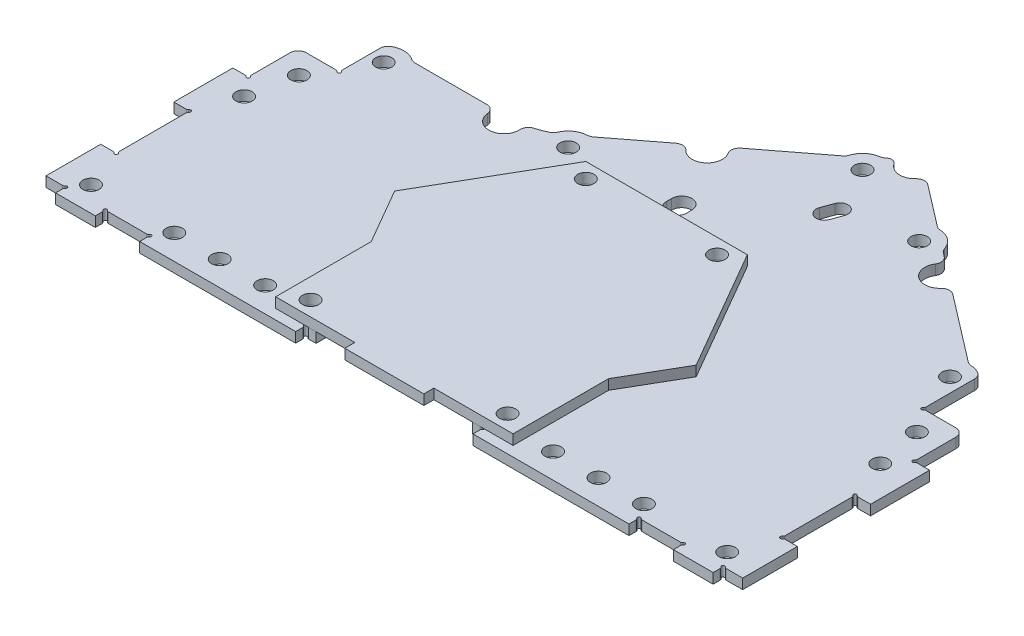
SolidWorks part; units mm, degrees
material "Alum Plate"
ref_plane "Front Plane" through (0, 0, 0) normal (0, 0, 1) x (1, 0, 0)
ref_plane "Top Plane" through (0, 0, 0) normal (0, 1, 0) x (1, 0, 0)
ref_plane "Right Plane" through (0, 0, 0) normal (1, 0, 0) x (0, 0, -1)
sketch "Top Layout" plane through (0, 0, 0) normal (0, 1, 0) x (1, 0, 0)
  line L0 (-114.046, -123.825) -> (-104.775, -123.825) construction
  line L1 (-104.775, -142.875) -> (-101.6, -142.875)
  line L2 (-104.775, -142.875) -> (-104.775, -104.775)
  line L3 (-104.775, -104.775) -> (-101.6, -104.775)
  line L4 (-101.6, -142.875) -> (-101.6, -104.775)
  line L5 (-104.775, -142.875) -> (-101.6, -104.775) construction
  line L6 (-104.775, -104.775) -> (-101.6, -142.875) construction
  line L7 (-19.05, -105.8164) -> (-101.6, -105.8164)
  line L8 (-19.05, -105.8164) -> (-19.05, -141.8336)
  line L9 (-19.05, -141.8336) -> (-101.6, -141.8336)
  line L10 (-101.6, -105.8164) -> (-101.6, -141.8336)
  line L11 (-19.05, -105.8164) -> (-101.6, -141.8336) construction
  line L12 (-19.05, -141.8336) -> (-101.6, -105.8164) construction
  line L13 (-133.096, -85.725) -> (-114.046, -85.725)
  line L14 (-133.096, -85.725) -> (-133.096, -161.925)
  line L15 (-133.096, -161.925) -> (-114.046, -161.925)
  line L16 (-114.046, -85.725) -> (-114.046, -161.925)
  line L17 (-133.096, -85.725) -> (-114.046, -161.925) construction
  line L18 (-133.096, -161.925) -> (-114.046, -85.725) construction
  line L19 (-104.775, -123.825) -> (0, -123.825) construction
  line L20 (0, -123.825) -> (0, 0) construction
  line L21 (-52.3528, -40.1717) -> (0, 0) construction
  line L22 (-70.6449, -16.3328) -> (-18.2922, 23.8388)
  line L23 (-34.0606, -64.0105) -> (18.2922, -23.8388)
  line L24 (-30.9251, 40.3023) -> (-122.2248, -29.7544)
  line L25 (-153.9748, -53.975) -> (-153.9748, -123.825)
  line L26 (-109.5248, -162.052) -> (109.5248, -162.052)
  line L27 (0, -162.052) -> (0, -123.825) construction
  line L28 (-109.5248, -162.052) -> (-109.5248, -20.0093) construction
  line L29 (-104.775, -142.875) -> (-104.775, -152.527)
  line L30 (-104.775, -152.527) -> (104.775, -152.527)
  line L31 (104.775, -104.775) -> (101.6, -104.775)
  line L32 (-144.4498, -73.025) -> (-109.5248, -73.025)
  line L33 (-144.4498, -73.025) -> (-144.4498, -123.825)
  line L34 (-144.4498, -123.825) -> (-109.5248, -123.825) construction
  line L35 (-109.5248, -73.025) -> (-109.5248, -162.052)
  line L36 (-144.4498, -73.025) -> (-109.5248, -123.825) construction
  line L37 (-144.4498, -123.825) -> (-109.5248, -73.025) construction
  line L38 (101.6, -142.875) -> (101.6, -104.775)
  line L39 (104.775, -142.875) -> (101.6, -142.875)
  line L40 (104.775, -142.875) -> (104.775, -104.775)
  line L41 (104.775, -142.875) -> (104.775, -152.527)
  line L42 (109.5248, -162.052) -> (109.5248, -20.0093) construction
  line L43 (30.9251, 40.3023) -> (122.2248, -29.7544)
  line L45 (19.05, -141.8336) -> (101.6, -141.8336)
  line L46 (101.6, -105.8164) -> (101.6, -141.8336)
  line L47 (19.05, -105.8164) -> (101.6, -105.8164)
  line L48 (19.05, -105.8164) -> (19.05, -141.8336)
  line L49 (133.096, -161.925) -> (114.046, -161.925)
  line L50 (114.046, -85.725) -> (114.046, -161.925)
  line L51 (133.096, -85.725) -> (114.046, -85.725)
  line L52 (133.096, -85.725) -> (133.096, -161.925)
  line L53 (144.4498, -123.825) -> (109.5248, -123.825) construction
  line L54 (109.5248, -73.025) -> (109.5248, -162.052)
  line L55 (144.4498, -73.025) -> (109.5248, -73.025)
  line L56 (144.4498, -73.025) -> (144.4498, -123.825)
  line L57 (-109.5248, -123.825) -> (-109.5248, -162.052) construction
  line L62 (-153.9748, -53.975) -> (-122.2248, -53.975)
  line L63 (-122.2248, -53.975) -> (-122.2248, -29.7544)
  line L64 (-144.4498, -123.825) -> (-153.9748, -123.825)
  line L65 (153.9748, -53.975) -> (153.9748, -123.825)
  line L66 (109.5248, -123.825) -> (109.5248, -162.052) construction
  line L67 (144.4498, -123.825) -> (153.9748, -123.825)
  line L68 (122.2248, -29.7544) -> (122.2248, -53.975)
  line L73 (-104.775, -104.775) -> (-104.775, -16.3647) construction
  line L74 (-95.25, -162.052) -> (-95.25, -9.0559) construction
  line L75 (-109.5248, -162.052) -> (-109.5248, -123.825) construction
  line L76 (109.5248, -162.052) -> (109.5248, -123.825) construction
  line L77 (122.2248, -53.975) -> (153.9748, -53.975)
  line L83 (104.775, -155.5496) -> (-104.775, -155.5496) construction
  line L88 (95.25, -162.052) -> (95.25, -9.0559) construction
  line L89 (104.775, -104.775) -> (104.775, -16.3647) construction
  line L92 (-104.775, -152.527) -> (-104.775, -162.052) construction
  line L93 (-14.605, -76.327) -> (14.605, -76.327)
  line L94 (-14.605, -76.327) -> (-14.605, -152.527)
  line L95 (-14.605, -152.527) -> (14.605, -152.527)
  line L96 (14.605, -76.327) -> (14.605, -152.527)
  line L97 (-14.605, -76.327) -> (14.605, -152.527) construction
  line L98 (-14.605, -152.527) -> (14.605, -76.327) construction
  line L99 (104.775, -152.527) -> (104.775, -162.052) construction
  line L100 (-19.05, -105.8164) -> (0, -105.8164) construction
  line L107 (0, -105.8164) -> (19.05, -105.8164) construction
  line L108 (104.775, -123.825) -> (114.046, -123.825) construction
  circle A0 centre (0, 0) radius 114.3
  circle A1 centre (0, 0) radius 6.35
  circle A2 centre (-52.3528, -40.1717) radius 17.8
  circle A3 centre (0, 0) radius 30.0482
  circle A4 centre (-52.3528, -40.1717) radius 30.0482
  arc A5 (-30.9251, 40.3023) -> (30.9251, 40.3023) centre (0, 0) cw
  point P2 (-103.1875, -123.825)
  point P7 (-60.325, -123.825)
  point P12 (-123.571, -123.825)
  point P30 (-126.9873, -98.425)
  point P35 (0, -114.427)
  point P53 (0, -152.527)
  dimension "D1" = 35.6
  dimension "D2" = 12.7
  dimension "D3" = 228.6
  dimension "D11" = 60.0964
  dimension "D12" = 50.8
  dimension "D14" = 52.5
  dimension "D4" = 3.175
  dimension "D5" = 19.05
  dimension "D6" = 76.2
  dimension "D7" = 82.55
  dimension "D8" = 38.1
  dimension "D9" = 104.775
  dimension "D10" = 18.0086
  dimension "D13" = 9.525
  dimension "D15" = 4.7498
  dimension "D16" = 9.525
  dimension "D17" = 9.652
  dimension "D18" = 50.8
  dimension "D19" = 12.446
  dimension "D20" = 65.9892
  dimension "D21" = 19.05
  dimension "D22" = 34.925
  dimension "D23" = 123.825
  dimension "D24" = 12.7
  dimension "D25" = 9.525
  dimension "D26" = 29.21
  dimension "D27" = 76.2
  dimension "D28" = 3.0226
sketch "Side Layout" plane through (0, 0, 0) normal (1, 0, 0) x (0, 0, -1)
  line L0 (0, -38.1) -> (0, 33.7344) construction
  line L1 (-114.3, -20.955) -> (114.3, -20.955)
  line L2 (-114.3, -20.955) -> (-114.3, -33.655)
  line L3 (-114.3, -33.655) -> (114.3, -33.655)
  line L4 (114.3, -20.955) -> (114.3, -33.655)
  line L5 (-114.3, -20.955) -> (114.3, -33.655) construction
  line L6 (-114.3, -33.655) -> (114.3, -20.955) construction
  line L7 (-9.525, -32.9406) -> (9.525, -32.9406)
  line L8 (-9.525, -32.9406) -> (-9.525, -38.1)
  line L9 (-9.525, -38.1) -> (9.525, -38.1)
  line L10 (9.525, -32.9406) -> (9.525, -38.1)
  line L11 (-9.525, -32.9406) -> (9.525, -38.1) construction
  line L12 (-9.525, -38.1) -> (9.525, -32.9406) construction
  line L13 (-11.9126, -29.3338) -> (11.9126, -29.3338)
  line L14 (-11.9126, -29.3338) -> (-11.9126, -32.9406)
  line L15 (-11.9126, -32.9406) -> (11.9126, -32.9406)
  line L16 (11.9126, -29.3338) -> (11.9126, -32.9406)
  line L17 (-11.9126, -29.3338) -> (11.9126, -32.9406) construction
  line L18 (-11.9126, -32.9406) -> (11.9126, -29.3338) construction
  line L19 (-6.35, -32.9406) -> (6.35, -32.9406)
  line L20 (-6.35, -32.9406) -> (-6.35, 33.7344)
  line L21 (-6.35, 33.7344) -> (6.35, 33.7344)
  line L22 (6.35, -32.9406) -> (6.35, 33.7344)
  line L23 (-6.35, -32.9406) -> (6.35, 33.7344) construction
  line L24 (-6.35, 33.7344) -> (6.35, -32.9406) construction
  line L25 (-162.052, 0) -> (-123.825, 0) construction
  line L26 (114.3, -33.655) -> (114.3, 0) construction
  line L27 (-142.875, 19.05) -> (-104.775, 19.05)
  line L28 (-40.1717, -9.525) -> (-40.1717, 5.4) construction
  line L29 (-142.875, 19.05) -> (-142.875, -19.05)
  line L30 (-142.875, -19.05) -> (-104.775, -19.05)
  line L31 (-104.775, 19.05) -> (-104.775, -19.05)
  line L32 (-142.875, 19.05) -> (-104.775, -19.05) construction
  line L33 (-142.875, -19.05) -> (-104.775, 19.05) construction
  line L34 (-130.175, -38.1) -> (-117.9516, -38.1) construction
  line L35 (-57.9717, -14.6) -> (-22.3717, -14.6)
  line L36 (-30.0482, -2.794) -> (30.0482, -2.794)
  line L37 (-30.0482, -2.794) -> (-30.0482, -20.955)
  line L38 (-30.0482, -20.955) -> (30.0482, -20.955)
  line L39 (30.0482, -2.794) -> (30.0482, -20.955)
  line L40 (-30.0482, -2.794) -> (30.0482, -20.955) construction
  line L41 (-30.0482, -20.955) -> (30.0482, -2.794) construction
  line L42 (-30.0482, -2.794) -> (-30.0482, 0) construction
  line L43 (-123.825, 0) -> (0, 0) construction
  line L44 (-57.9717, -14.6) -> (-57.9717, 25.4)
  line L45 (-57.9717, 25.4) -> (-22.3717, 25.4)
  line L46 (-22.3717, -14.6) -> (-22.3717, 25.4)
  line L47 (-19.05, 0) -> (19.05, 0)
  line L48 (-19.05, 0) -> (-19.05, -1.9812)
  line L49 (-19.05, -1.9812) -> (19.05, -1.9812)
  line L50 (19.05, 0) -> (19.05, -1.9812)
  line L51 (-19.05, 0) -> (19.05, -1.9812) construction
  line L52 (-19.05, -1.9812) -> (19.05, 0) construction
  line L53 (-70.2199, -3.175) -> (-10.1235, -3.175)
  line L54 (-70.2199, -3.175) -> (-70.2199, -15.875)
  line L55 (-70.2199, -15.875) -> (-10.1235, -15.875)
  line L56 (-10.1235, -3.175) -> (-10.1235, -15.875)
  line L57 (-70.2199, -3.175) -> (-10.1235, -15.875) construction
  line L58 (-70.2199, -15.875) -> (-10.1235, -3.175) construction
  line L59 (-40.1717, -9.525) -> (-40.1717, 0) construction
  line L60 (-57.9717, -14.6) -> (-22.3717, 25.4) construction
  line L61 (-57.9717, 25.4) -> (-22.3717, -14.6) construction
  line L62 (-22.3717, 0) -> (-57.9717, 0) construction
  line L63 (-137.8162, 0) -> (-123.825, -13.9912) construction
  line L64 (-139.065, 15.24) -> (-108.585, 15.24) construction
  line L65 (-139.065, 15.24) -> (-139.065, -15.24) construction
  line L66 (-139.065, -15.24) -> (-108.585, -15.24) construction
  line L67 (-108.585, 15.24) -> (-108.585, -15.24) construction
  line L68 (-139.065, 15.24) -> (-108.585, -15.24) construction
  line L69 (-139.065, -15.24) -> (-108.585, 15.24) construction
  line L70 (-137.8162, 0) -> (-123.825, 13.9912) construction
  line L71 (-123.825, -13.9912) -> (-109.8338, 0) construction
  line L72 (-123.825, 13.9912) -> (-109.8338, 0) construction
  line L73 (-137.8162, 0) -> (-109.8338, 0) construction
  line L74 (-123.825, -13.9912) -> (-123.825, 13.9912) construction
  line L75 (-6.35, 17.8594) -> (6.35, 17.8594)
  line L76 (114.3, 0) -> (-114.3, 0) construction
  line L77 (-22.3717, 19.05) -> (-6.35, 19.05) construction
  line L78 (-123.825, 38.1) -> (-97.9206, 38.1) construction
  line L79 (-19.05, -3.5814) -> (19.05, -3.5814)
  line L80 (-19.05, -3.5814) -> (-19.05, -1.9812)
  line L81 (-19.05, -1.9812) -> (19.05, -1.9812)
  line L82 (19.05, -3.5814) -> (19.05, -1.9812)
  line L83 (-19.05, -3.5814) -> (19.05, -1.9812) construction
  line L84 (-19.05, -1.9812) -> (19.05, -3.5814) construction
  line L85 (-8.7376, -16.7608) -> (8.7376, -16.7608)
  line L86 (-8.7376, -16.7608) -> (-8.7376, -29.3338)
  line L87 (-8.7376, -29.3338) -> (8.7376, -29.3338)
  line L88 (8.7376, -16.7608) -> (8.7376, -29.3338)
  line L89 (-8.7376, -16.7608) -> (8.7376, -29.3338) construction
  line L90 (-8.7376, -29.3338) -> (8.7376, -16.7608) construction
  line L91 (-8.7376, -3.5814) -> (8.7376, -3.5814)
  line L92 (-8.7376, -3.5814) -> (-8.7376, -16.1544)
  line L93 (-8.7376, -16.1544) -> (8.7376, -16.1544)
  line L94 (8.7376, -3.5814) -> (8.7376, -16.1544)
  line L95 (-8.7376, -3.5814) -> (8.7376, -16.1544) construction
  line L96 (-8.7376, -16.1544) -> (8.7376, -3.5814) construction
  circle A0 centre (-123.825, 0) radius 18.0086
  circle A1 centre (-123.825, 0) radius 38.1
  circle A2 centre (-139.065, 15.24) radius 1.905
  circle A3 centre (-108.585, 15.24) radius 1.905
  circle A4 centre (-108.585, -15.24) radius 1.905
  circle A5 centre (-139.065, -15.24) radius 1.905
  circle A6 centre (-137.8162, 0) radius 1.6002
  circle A7 centre (-123.825, 13.9912) radius 1.6002
  circle A8 centre (-109.8338, 0) radius 1.6002
  circle A9 centre (-123.825, -13.9912) radius 1.6002
  point P0 (0, -27.305)
  point P6 (0, -31.1372)
  point P7 (0, -35.5203)
  point P21 (0, 0.3969)
  point P32 (0, -11.8745)
  point P43 (0, -0.9906)
  point P55 (-40.1717, -9.525)
  point P72 (-40.1717, 5.4)
  point P88 (0, -23.0473)
  point P93 (0, -2.7813)
  point P102 (0, -9.8679)
  dimension "D17" = 3.81
  dimension "D18" = 3.2004
  dimension "D1" = 12.7
  dimension "D2" = 5.1594
  dimension "D3" = 19.05
  dimension "D4" = 3.6068
  dimension "D5" = 23.8252
  dimension "D6" = 12.7
  dimension "D7" = 18.161
  dimension "D8" = 1.9812
  dimension "D9" = 12.7
  dimension "D10" = 40
  dimension "D11" = 25.4
  dimension "D12" = 50.8
  dimension "D13" = 41.275
  dimension "D14" = 30.48
  dimension "D15" = 4.445
  dimension "D16" = 19.7866
  dimension "D19" = 15.875
  dimension "D20" = 6.35
  dimension "D21" = 38.1
  dimension "D22" = 1.6002
  dimension "D23" = 38.1
  dimension "D24" = 17.4752
  dimension "D25" = 12.573
ref_plane "Plane1" through (0, 25.4, 0) normal (0, 1, 0) x (1, 0, 0)
sketch "Sketch3" plane through (0, 25.4, 0) normal (0, 1, 0) x (1, 0, 0)
  line L0 (-104.775, -36.3747) -> (-30.9251, 20.2924)
  line L1 (-104.775, -104.775) -> (-104.775, -16.3647) construction
  line L2 (0, -200130.175) -> (0, 199882.0484) construction
  line L3 (-30.9251, 40.3023) -> (-122.2248, -29.7544) construction
  line L5 (-104.775, -36.3747) -> (-104.775, -77.6497)
  line L6 (-92.075, -77.6497) -> (-104.775, -77.6497)
  line L7 (30.9251, 20.2924) -> (104.775, -36.3747)
  line L8 (104.775, -77.6497) -> (92.075, -77.6497)
  line L9 (104.775, -36.3747) -> (104.775, -77.6497)
  line L11 (104.775, -104.775) -> (104.775, -16.3647) construction
  line L12 (30.9251, 40.3023) -> (122.2248, -29.7544) construction
  line L13 (92.075, -74.6536) -> (24.1423, -22.5271)
  line L14 (-32.2514, -66.3682) -> (20.1013, -26.1965)
  line L15 (-30.9251, 20.2924) -> (0, 44.022)
  line L16 (0, 44.022) -> (30.9251, 20.2924)
  line L17 (-92.075, -77.6497) -> (-92.075, -73.1917)
  line L19 (-92.075, -73.1917) -> (-52.3528, -73.1917)
  line L20 (92.075, -74.6536) -> (92.075, -77.6497)
  circle A0 centre (-52.3528, -40.1717) radius 17.8 construction
  circle A1 centre (-52.3528, -40.1717) radius 17.8
  circle A2 centre (0, 0) radius 6.35
  circle A3 centre (0, 0) radius 6.35 construction
  arc A4 (-52.3528, -73.1917) -> (-32.2514, -66.3682) centre (-52.3528, -40.1717) ccw
  arc A5 (20.1013, -26.1965) -> (24.1423, -22.5271) centre (0, 0) ccw
  arc A6 (30.9251, 20.2924) -> (-30.9251, 20.2924) centre (0, -20.01) ccw construction
  point P28 (0, 44.022)
  dimension "D1" = 33.02
  dimension "D5" = 50.8
  dimension "D2" = 41.275
  dimension "D3" = 34.925
  dimension "D4" = 12.7
  dimension "D6" = 38.1
ref_plane "Plane3" through (-104.775, 0, 0) normal (-1, 0, 0) x (0, 0, 1)
sketch "Sketch6" plane through (-104.775, 0, 0) normal (-1, 0, 0) x (0, 0, 1)
  line L0 (162.052, -25.4) -> (162.052, 25.4)
  line L1 (162.052, 25.4) -> (77.6497, 25.4)
  line L2 (36.3747, 25.4) -> (77.6497, 25.4) construction
  line L3 (147.7645, 11.1125) -> (162.052, 11.1125) construction
  line L4 (162.052, 0) -> (71.2997, 0) construction
  line L5 (77.6497, 25.4) -> (77.6497, 19.05)
  line L6 (77.6497, 19.05) -> (36.3747, 19.05)
  line L7 (36.3747, 19.05) -> (36.3747, 6.35)
  line L8 (36.3747, 6.35) -> (71.2997, 6.35)
  line L10 (99.6315, -3.175) -> (99.6315, 11.1125) construction
  line L11 (71.2997, -25.4) -> (162.052, -25.4)
  line L13 (71.2997, 6.35) -> (71.2997, -25.4)
  line L14 (152.527, -25.4) -> (152.527, 25.4) construction
  line L15 (99.6315, 11.1125) -> (99.6315, 25.4) construction
  line L16 (147.7645, 11.1125) -> (147.7645, 25.4) construction
  line L17 (94.869, -7.9375) -> (104.394, -7.9375) construction
  line L18 (94.869, -7.9375) -> (94.869, 25.4) construction
  line L19 (94.869, 25.4) -> (104.394, 25.4) construction
  line L20 (104.394, -7.9375) -> (104.394, 25.4) construction
  line L21 (94.869, -7.9375) -> (104.394, 25.4) construction
  line L22 (94.869, 25.4) -> (104.394, -7.9375) construction
  line L23 (147.7645, 11.1125) -> (147.7645, -3.175) construction
  line L24 (104.394, -7.9375) -> (123.825, -7.9375) construction
  line L25 (143.002, -7.9375) -> (152.527, -7.9375) construction
  line L26 (143.002, -7.9375) -> (143.002, 25.4) construction
  line L27 (143.002, 25.4) -> (152.527, 25.4) construction
  line L28 (152.527, -7.9375) -> (152.527, 25.4) construction
  line L29 (143.002, -7.9375) -> (152.527, 25.4) construction
  line L30 (143.002, 25.4) -> (152.527, -7.9375) construction
  line L31 (123.825, -7.9375) -> (152.527, -7.9375) construction
  line L32 (104.775, 19.05) -> (104.775, -19.05) construction
  line L34 (155.702, -25.4) -> (155.702, 25.4) construction
  circle A0 centre (109.8338, 0) radius 1.6002 construction
  circle A1 centre (123.825, 13.9912) radius 1.6002 construction
  circle A2 centre (137.8162, 0) radius 1.6002 construction
  circle A3 centre (123.825, -13.9912) radius 1.6002 construction
  circle A4 centre (109.8338, 0) radius 1.6002 construction
  circle A5 centre (123.825, 13.9912) radius 1.6002 construction
  circle A6 centre (137.8162, 0) radius 1.6002 construction
  circle A7 centre (123.825, -13.9912) radius 1.6002 construction
  circle A8 centre (123.825, 0) radius 18.0086 construction
  circle A9 centre (123.825, 0) radius 18.0086 construction
  circle A10 centre (123.825, 0) radius 9.525
  circle A11 centre (108.585, -15.24) radius 1.905 construction
  circle A12 centre (108.585, 15.24) radius 1.905 construction
  circle A13 centre (139.065, 15.24) radius 1.905 construction
  circle A14 centre (139.065, -15.24) radius 1.905 construction
  circle A15 centre (108.585, -15.24) radius 1.905
  circle A16 centre (108.585, 15.24) radius 1.905
  circle A17 centre (139.065, 15.24) radius 1.905
  circle A18 centre (139.065, -15.24) radius 1.905
  circle A19 centre (147.7645, 11.1125) radius 2.5527
  circle A26 centre (99.6315, 11.1125) radius 2.5527
  circle A27 centre (99.6315, -3.175) radius 2.5527
  circle A28 centre (147.7645, -3.175) radius 2.5527
  point P29 (0, 0)
  point P55 (99.6315, 8.7312)
  point P61 (147.7645, 8.7312)
  dimension "D4" = 19.05
  dimension "D7" = 5.1054
  dimension "D1" = 6.35
  dimension "D2" = 12.7
  dimension "D3" = 25.4
  dimension "D5" = 6.35
  dimension "D6" = 3.175
  dimension "D8" = 0.381
  dimension "D9" = 14.2875
  dimension "D10" = 9.525
  dimension "D12" = 33.3375
ref_plane "Plane4" through (0, 19.05, 0) normal (0, 1, 0) x (1, 0, 0)
sketch "Sketch12" plane through (0, 19.05, 0) normal (0, 1, 0) x (1, 0, 0)
  line L0 (-104.775, -77.6497) -> (-104.775, -36.3747)
  line L1 (-104.775, -36.3747) -> (-92.075, -36.3747)
  line L3 (-92.075, -36.3747) -> (-92.075, -77.6497)
  line L5 (-92.075, -77.6497) -> (-104.775, -77.6497)
  line L6 (-98.425, -77.6497) -> (-98.425, -63.3622) construction
  line L7 (-98.425, -63.3622) -> (-98.425, -50.6622) construction
  line L8 (-98.425, -50.6622) -> (-98.425, -36.3747) construction
  line L10 (-98.425, -36.3747) -> (-104.775, -36.3747) construction
  circle A0 centre (-98.425, -63.3622) radius 2.5527
  circle A1 centre (-98.425, -50.6622) radius 2.5527
  dimension "D2" = 5.1054
  dimension "D1" = 12.7
  dimension "D3" = 12.7
sketch "Sketch25" plane through (0, 25.4, 0) normal (0, 1, 0) x (1, 0, 0)
  line L0 (-104.775, -152.527) -> (104.775, -152.527)
  line L1 (-104.775, -152.527) -> (104.775, -152.527) construction
  line L2 (104.775, -152.527) -> (104.775, -162.052)
  line L3 (104.775, -162.052) -> (-104.775, -162.052)
  line L4 (-104.775, -162.052) -> (-104.775, -152.527)
ref_plane "Plane5" through (0, 0, 152.527) normal (0, 0, 1) x (1, 0, 0)
sketch "Sketch41" plane through (0, 0, 152.527) normal (0, 0, 1) x (1, 0, 0)
  line L0 (-104.775, -7.9375) -> (-104.775, 25.4) construction
  line L1 (-104.775, -7.9375) -> (-104.775, 12.7)
  line L2 (-104.775, -7.9375) -> (104.775, -7.9375)
  line L3 (104.775, -7.9375) -> (104.775, 12.7)
  line L4 (104.775, 25.4) -> (-104.775, 25.4)
  line L5 (0, -7.9375) -> (0, 25.4) construction
  line L6 (-104.775, 3.9624) -> (-100.0125, 3.9624) construction
  line L7 (-100.0125, 3.9624) -> (-100.0125, 25.4) construction
  line L8 (104.775, 3.9624) -> (100.0125, 3.9624) construction
  line L9 (100.0125, 3.9624) -> (100.0125, 25.4) construction
  line L10 (19.05, 20.6375) -> (23.8252, 20.6375) construction
  line L11 (19.05, 15.875) -> (78.5876, 15.875) construction
  line L12 (19.05, 15.875) -> (19.05, 25.4) construction
  line L13 (19.05, 25.4) -> (78.5876, 25.4) construction
  line L14 (78.5876, 15.875) -> (78.5876, 25.4) construction
  line L15 (19.05, 15.875) -> (78.5876, 25.4) construction
  line L16 (19.05, 25.4) -> (78.5876, 15.875) construction
  line L17 (23.8252, 20.6375) -> (38.1127, 20.6375) construction
  line L18 (38.1127, 20.6375) -> (52.4002, 20.6375) construction
  line L19 (52.4002, 20.6375) -> (66.6877, 20.6375) construction
  line L20 (-104.775, 25.4) -> (-112.395, 25.4)
  line L21 (-112.395, 25.4) -> (-112.395, 3.175)
  line L22 (-112.395, 3.175) -> (-109.5248, 3.175)
  line L23 (-109.5248, 3.175) -> (-109.5248, 12.7)
  line L24 (-109.5248, 12.7) -> (-104.775, 12.7)
  line L25 (-104.775, 12.7) -> (-104.775, 25.4) construction
  line L26 (104.775, 25.4) -> (112.395, 25.4)
  line L27 (112.395, 25.4) -> (112.395, 3.175)
  line L28 (112.395, 3.175) -> (109.5248, 3.175)
  line L29 (109.5248, 3.175) -> (109.5248, 12.7)
  line L30 (109.5248, 12.7) -> (104.775, 12.7)
  line L31 (104.775, 12.7) -> (104.775, 25.4) construction
  line L32 (-100.0125, 3.9624) -> (-87.3125, 3.9624) construction
  line L33 (-63.5, -1.5875) -> (0, -1.5875) construction
  line L34 (0, -1.5875) -> (63.5, -1.5875) construction
  line L35 (63.5, -1.5875) -> (63.5, -7.9375) construction
  circle A0 centre (-100.0125, 3.9624) radius 2.5527
  circle A1 centre (100.0125, 3.9624) radius 2.5527
  circle A2 centre (23.8252, 20.6375) radius 2.5527
  circle A3 centre (38.1127, 20.6375) radius 2.5527
  circle A4 centre (52.4002, 20.6375) radius 2.5527
  circle A5 centre (66.6877, 20.6375) radius 2.5527
  circle A6 centre (-66.6877, 20.6375) radius 2.5527
  circle A7 centre (-52.4002, 20.6375) radius 2.5527
  circle A8 centre (-38.1127, 20.6375) radius 2.5527
  circle A9 centre (-23.8252, 20.6375) radius 2.5527
  circle A10 centre (-87.3125, 3.9624) radius 2.5527
  circle A11 centre (87.3125, 3.9624) radius 2.5527
  circle A12 centre (-63.5, -1.5875) radius 2.5527
  circle A13 centre (63.5, -1.5875) radius 2.5527
  point P14 (48.8188, 20.6375)
  dimension "D3" = 5.1054
  dimension "D7" = 5.1054
  dimension "D1" = 21.4376
  dimension "D2" = 4.7625
  dimension "D4" = 9.525
  dimension "D5" = 59.5376
  dimension "D6" = 4.7752
  dimension "D8" = 14.2875
  dimension "D9" = 7.62
  dimension "D10" = 4.7498
  dimension "D11" = 12.7
  dimension "D12" = 9.525
  dimension "D13" = 19.05
  dimension "D14" = 12.7
  dimension "D15" = 6.35
  dimension "D16" = 63.5
sketch "Sketch44" plane through (0, 25.4, 0) normal (0, 1, 0) x (1, 0, 0)
  line L0 (73.8315, -147.7645) -> (73.8315, -152.527) construction
  line L1 (92.075, -74.6536) -> (92.075, -77.6497) construction
  line L2 (-92.075, -77.6497) -> (-92.075, -73.1917) construction
  line L3 (0, -123.825) -> (0, 0) construction
  line L4 (-92.075, -73.1917) -> (-52.3528, -73.1917) construction
  line L5 (-104.775, -104.775) -> (-104.775, -16.3647) construction
  line L6 (-32.2514, -66.3682) -> (20.1013, -26.1965) construction
  line L21 (-104.775, -68.1247) -> (-104.775, -152.527)
  line L22 (-104.775, -152.527) -> (104.775, -152.527)
  line L23 (104.775, -152.527) -> (104.775, -68.1247)
  line L34 (-104.775, -99.6315) -> (-100.0125, -99.6315) construction
  line L35 (-104.775, -147.7645) -> (-100.0125, -147.7645) construction
  line L36 (0, -152.527) -> (0, -35.6178) construction
  line L38 (30.969, -147.7645) -> (45.2565, -147.7645) construction
  line L39 (45.2565, -147.7645) -> (59.544, -147.7645) construction
  line L40 (59.544, -147.7645) -> (73.8315, -147.7645) construction
  line L41 (23.8252, -152.527) -> (30.969, -152.527) construction
  line L42 (104.775, -152.527) -> (-104.775, -152.527) construction
  line L43 (30.969, -152.527) -> (38.1127, -152.527) construction
  line L44 (30.969, -152.527) -> (30.969, -147.7645) construction
  line L45 (-92.075, -77.6497) -> (-104.775, -77.6497) construction
  line L48 (-35.1507, -62.5899) -> (-8.9743, -42.504) construction
  line L49 (-8.9743, -42.504) -> (17.2021, -22.4182) construction
  line L50 (45.5313, -32.9364) -> (87.3125, -64.9962) construction
  line L51 (92.075, -74.6536) -> (24.1423, -22.5271) construction
  line L52 (104.775, -77.6497) -> (92.075, -77.6497) construction
  line L79 (-104.775, -68.1247) -> (-92.075, -68.1247)
  line L80 (-92.075, -68.1247) -> (-92.075, -63.6667)
  line L85 (21.8118, -8.7328) -> (92.075, -62.6476)
  line L86 (-38.0499, -58.8115) -> (14.3028, -18.6398)
  line L87 (-92.075, -63.6667) -> (-52.3528, -63.6667)
  line L88 (92.075, -62.6476) -> (92.075, -68.1247)
  line L89 (92.075, -68.1247) -> (104.775, -68.1247)
  circle A0 centre (-73.8315, -147.7645) radius 2.5527
  circle A1 centre (-59.544, -147.7645) radius 2.5527
  circle A2 centre (-45.2565, -147.7645) radius 2.5527
  circle A3 centre (-30.969, -147.7645) radius 2.5527
  circle A17 centre (-100.0125, -99.6315) radius 2.5527
  circle A18 centre (-100.0125, -147.7645) radius 2.5527
  circle A19 centre (100.0125, -147.7645) radius 2.5527
  circle A20 centre (100.0125, -99.6315) radius 2.5527
  circle A21 centre (30.969, -147.7645) radius 2.5527
  circle A22 centre (45.2565, -147.7645) radius 2.5527
  circle A23 centre (59.544, -147.7645) radius 2.5527
  circle A24 centre (73.8315, -147.7645) radius 2.5527
  circle A25 centre (-87.3125, -68.4292) radius 4.7625 construction
  circle A26 centre (-35.1507, -62.5899) radius 4.7625 construction
  circle A27 centre (-8.9743, -42.504) radius 4.7625 construction
  circle A28 centre (17.2021, -22.4182) radius 4.7625 construction
  circle A29 centre (45.5313, -32.9364) radius 4.7625 construction
  circle A30 centre (87.3125, -64.9962) radius 4.7625 construction
  circle A32 centre (-87.3125, -68.4292) radius 2.5527
  circle A33 centre (-35.1507, -62.5899) radius 2.5527
  circle A34 centre (-8.9743, -42.504) radius 2.5527 construction
  circle A35 centre (17.2021, -22.4182) radius 2.5527
  circle A36 centre (45.5313, -32.9364) radius 2.5527
  circle A37 centre (87.3125, -64.9962) radius 2.5527
  circle A38 centre (-97.155, -85.2697) radius 7.62 construction
  circle A39 centre (97.155, -85.2697) radius 7.62 construction
  circle A40 centre (24.4294, -36.7543) radius 11.1125 construction
  arc A41 (20.1013, -26.1965) -> (24.1423, -22.5271) centre (0, 0) ccw construction
  circle A42 centre (-97.155, -85.2697) radius 2.5527
  circle A43 centre (24.4294, -36.7543) radius 2.5527
  circle A44 centre (97.155, -85.2697) radius 2.5527
  arc A56 (14.3028, -18.6398) -> (21.8118, -8.7328) centre (0, 0) ccw
  arc A57 (-52.3528, -63.6667) -> (-38.0499, -58.8115) centre (-52.3528, -40.1717) ccw
  point P4 (-104.775, -152.527)
  dimension "D2" = 5.1054
  dimension "D7" = 5.1054
  dimension "D8" = 15.24
  dimension "D3" = 9.525
  dimension "D9" = 9.525
  dimension "D11" = 22.225
  dimension "D4" = 4.7625
  dimension "D5" = 14.2875
  dimension "D6" = 9.525
  dimension "D1" = 4.7625
  dimension "D10" = 52.664
extrude "Top Plate Extrude-----------" add sketch "Sketch44" along normal blind 3.175
sketch "Sketch82" plane through (0, 28.575, 0) normal (0, 1, 0) x (1, 0, 0)
  line L0 (-52.3528, -63.6667) -> (-92.075, -63.6667) construction
  line L1 (-52.3528, -65.5717) -> (-52.3528, -63.6667) construction
  line L2 (-12.4467, -41.5667) -> (-13.6064, -40.0553) construction
  line L3 (14.3028, -18.6398) -> (-38.0499, -58.8115) construction
  line L4 (24.5175, -13.2101) -> (25.6772, -11.6988) construction
  line L5 (92.075, -62.6476) -> (21.8118, -8.7328) construction
  line L6 (58.2962, -39.1295) -> (59.4559, -37.6181) construction
  line L7 (21.4643, -9.5551) -> (21.8118, -8.7328)
  line L8 (21.8118, -8.7328) -> (22.2143, -9.0416)
  circle A0 centre (-52.3528, -65.5717) radius 4.7625
  circle A1 centre (-12.4467, -41.5667) radius 4.7625
  arc A2 (21.4643, -9.5551) -> (22.2143, -9.0416) centre (24.5175, -13.2101) ccw
  circle A3 centre (58.2962, -39.1295) radius 4.7625
  arc A4 (14.3028, -18.6398) -> (21.8118, -8.7328) centre (0, 0) ccw construction
  dimension "D1" = 9.525
  dimension "D2" = 1.905
  dimension "D3" = 30.8104
  dimension "D4" = 83.6926
  dimension "D5" = 41.1154
extrude "Cut-Extrude38" cut sketch "Sketch82" against normal up to surface (3.175 mm away) up to face at (-4.435, 25.4, 71.2837)
sketch "Sketch72" plane through (0, 25.4, 0) normal (0, 1, 0) x (1, 0, 0)
  line L0 (-104.775, -68.1247) -> (-104.775, -152.527) construction
  line L1 (-104.775, -152.527) -> (-109.5248, -152.527)
  line L2 (-104.775, -152.527) -> (-104.775, -135.0645)
  line L3 (-104.775, -135.0645) -> (-109.5248, -135.0645)
  line L4 (-109.5248, -152.527) -> (-109.5248, -135.0645)
  line L5 (-104.775, -152.527) -> (-109.5248, -135.0645) construction
  line L6 (-104.775, -135.0645) -> (-109.5248, -152.527) construction
  line L7 (-104.775, -152.527) -> (104.775, -152.527) construction
  line L8 (-77.0065, -152.527) -> (-73.8315, -147.7645) construction
  line L9 (-77.0065, -152.527) -> (-27.794, -152.527)
  line L10 (-77.0065, -152.527) -> (-77.0065, -155.5496)
  line L11 (-77.0065, -155.5496) -> (-27.794, -155.5496)
  line L12 (-27.794, -152.527) -> (-27.794, -155.5496)
  line L13 (-77.0065, -152.527) -> (-27.794, -155.5496) construction
  line L14 (-77.0065, -155.5496) -> (-27.794, -152.527) construction
  line L15 (-27.794, -152.527) -> (-30.969, -147.7645) construction
  line L16 (-77.0065, -152.527) -> (-77.0065, -147.7645) construction
  line L18 (-104.775, -93.5247) -> (-109.5248, -93.5247)
  line L19 (-104.775, -93.5247) -> (-104.775, -112.3315)
  line L20 (-104.775, -112.3315) -> (-109.5248, -112.3315)
  line L21 (-109.5248, -93.5247) -> (-109.5248, -112.3315)
  line L22 (-104.775, -93.5247) -> (-109.5248, -112.3315) construction
  line L23 (-104.775, -112.3315) -> (-109.5248, -93.5247) construction
  line L24 (0, -152.527) -> (-12.7, -152.527)
  line L25 (0, -152.527) -> (0, -155.5496)
  line L26 (0, -155.5496) -> (-12.7, -155.5496)
  line L27 (-12.7, -152.527) -> (-12.7, -155.5496)
  line L28 (0, -152.527) -> (-12.7, -155.5496) construction
  line L29 (0, -155.5496) -> (-12.7, -152.527) construction
  line L30 (-104.775, -68.1247) -> (-109.5248, -68.1247)
  line L31 (-104.775, -68.1247) -> (-104.775, -77.6497)
  line L32 (-104.775, -77.6497) -> (-109.5248, -77.6497)
  line L33 (-109.5248, -68.1247) -> (-109.5248, -77.6497)
  line L34 (-104.775, -68.1247) -> (-109.5248, -77.6497) construction
  line L35 (-104.775, -77.6497) -> (-109.5248, -68.1247) construction
  line L38 (-103.505, -155.5496) -> (-90.805, -155.5496)
  line L39 (-90.805, -152.527) -> (-90.805, -155.5496)
  line L40 (-103.505, -155.5496) -> (-103.505, -152.527)
  line L41 (-103.505, -155.5496) -> (-90.805, -152.527) construction
  line L42 (-103.505, -152.527) -> (-90.805, -152.527)
  line L43 (-77.0065, -147.7645) -> (-73.8315, -147.7645) construction
  line L44 (-103.505, -152.527) -> (-101.5221, -149.823) construction
  circle A0 centre (-100.0125, -147.7645) radius 2.5527 construction
  circle A1 centre (-73.8315, -147.7645) radius 2.5527 construction
  circle A2 centre (-30.969, -147.7645) radius 2.5527 construction
  point P4 (-107.1499, -143.7958)
  point P5 (-100.0125, -147.7645)
  point P16 (-52.4002, -154.0383)
  point P18 (-97.155, -154.0383)
  point P25 (-107.1499, -102.9281)
  point P34 (-6.35, -154.0383)
  point P39 (-107.1499, -72.8872)
  dimension "D1" = 4.7498
  dimension "D2" = 12.7
  dimension "D3" = 12.7
  dimension "D4" = 12.7
  dimension "D5" = 9.525
  dimension "D6" = 15.875
  dimension "D7" = 12.7
  dimension "D8" = 3.175
  dimension "D9" = 1.27
  dimension "D10" = 3.0226
extrude "Boss-Extrude27" add sketch "Sketch72" along normal through all
mirror "Mirror22" about plane through (0, 0, 0) normal (1, 0, 0) of "Boss-Extrude27"
sketch "Sketch86" plane through (0, 28.575, 0) normal (0, 1, 0) x (1, 0, 0)
  circle A0 centre (87.3125, -64.9962) radius 6.35
  circle A3 centre (17.2021, -22.4182) radius 6.35
  circle A4 centre (45.5313, -32.9364) radius 6.35
  circle A5 centre (-35.1507, -62.5899) radius 6.35
  circle A6 centre (-87.3125, -68.4292) radius 6.35
  circle A7 centre (87.3125, -64.9962) radius 2.5527 construction
  circle A8 centre (45.5313, -32.9364) radius 2.5527 construction
  circle A9 centre (17.2021, -22.4182) radius 2.5527 construction
  circle A10 centre (-35.1507, -62.5899) radius 2.5527 construction
  circle A11 centre (-87.3125, -68.4292) radius 2.5527 construction
  circle A12 centre (87.3125, -64.9962) radius 2.5527
  circle A13 centre (45.5313, -32.9364) radius 2.5527
  circle A14 centre (17.2021, -22.4182) radius 2.5527
  circle A15 centre (-35.1507, -62.5899) radius 2.5527
  circle A16 centre (-87.3125, -68.4292) radius 2.5527
  dimension "D1" = 12.7
extrude "Boss-Extrude31" add sketch "Sketch86" against normal through all
ref_plane "Plane8" through (0, 28.829, 0) normal (0, 1, 0) x (1, 0, 0)
sketch "Sketch87" plane through (0, 28.829, 0) normal (0, 1, 0) x (1, 0, 0)
  line L0 (0, -123.825) -> (0, 0) construction
  line L1 (-25.4, -66.802) -> (25.4, -66.802)
  line L2 (-25.4, -66.802) -> (-25.4, -143.002) construction
  line L3 (-25.4, -143.002) -> (25.4, -143.002)
  line L4 (25.4, -66.802) -> (25.4, -143.002) construction
  line L5 (-25.4, -66.802) -> (25.4, -143.002) construction
  line L6 (-25.4, -143.002) -> (25.4, -66.802) construction
  line L7 (-104.775, -152.527) -> (104.775, -152.527) construction
  line L8 (-25.4, -71.5645) -> (-20.6375, -71.5645) construction
  line L9 (-20.6375, -71.5645) -> (-20.6375, -66.802) construction
  line L10 (20.6375, -66.802) -> (20.6375, -71.5645) construction
  line L11 (20.6375, -71.5645) -> (25.4, -71.5645) construction
  line L12 (20.6375, -143.002) -> (20.6375, -138.2395) construction
  line L13 (20.6375, -138.2395) -> (25.4, -138.2395) construction
  line L14 (-20.6375, -143.002) -> (-20.6375, -138.2395) construction
  line L15 (-20.6375, -138.2395) -> (-25.4, -138.2395) construction
  line L16 (-25.4, -143.002) -> (-47.397, -104.902)
  line L17 (-47.397, -104.902) -> (-25.4, -66.802)
  line L18 (25.4, -66.802) -> (47.397, -104.902)
  line L19 (47.397, -104.902) -> (25.4, -143.002)
  circle A0 centre (-20.6375, -71.5645) radius 2.5527
  circle A1 centre (20.6375, -71.5645) radius 2.5527
  circle A3 centre (-20.6375, -138.2395) radius 2.5527
  circle A4 centre (20.6375, -138.2395) radius 2.5527
  point P0 (0, -104.902)
  dimension "D5" = 5.1054
  dimension "D1" = 50.8
  dimension "D2" = 9.525
  dimension "D3" = 76.2
  dimension "D4" = 4.7625
  dimension "D6" = 120
sketch "Sketch111" plane through (0, 28.575, 0) normal (0, 1, 0) x (1, 0, 0)
  line L0 (-109.5248, -77.6497) -> (-104.775, -77.6497) construction
  line L1 (-109.5248, -67.8707) -> (-91.7575, -67.8707)
  line L2 (-109.5248, -67.8707) -> (-109.5248, -77.9672)
  line L3 (-109.5248, -77.9672) -> (-91.7575, -77.9672)
  line L4 (-91.7575, -67.8707) -> (-91.7575, -77.9672)
  line L5 (-109.5248, -67.8707) -> (-91.7575, -77.9672) construction
  line L6 (-109.5248, -77.9672) -> (-91.7575, -67.8707) construction
  line L7 (109.5248, -67.8707) -> (91.7575, -67.8707)
  line L8 (109.5248, -67.8707) -> (109.5248, -77.9672)
  line L9 (109.5248, -77.9672) -> (91.7575, -77.9672)
  line L10 (91.7575, -67.8707) -> (91.7575, -77.9672)
  line L11 (109.5248, -67.8707) -> (91.7575, -77.9672) construction
  line L12 (109.5248, -77.9672) -> (91.7575, -67.8707) construction
  line L13 (-93.6552, -68.1247) -> (-109.5248, -68.1247) construction
  line L14 (-109.5248, -68.1247) -> (-109.5248, -77.6497) construction
  line L15 (109.5248, -68.1247) -> (109.5248, -77.6497) construction
  line L16 (-104.775, -104.775) -> (-104.775, -16.3647) construction
  point P4 (-100.6411, -72.9189)
  point P10 (100.6411, -72.9189)
  dimension "D1" = 13.0175
  dimension "D2" = 0.3175
  dimension "D3" = 0.254
extrude "Cut-Extrude57" cut sketch "Sketch111" against normal through all
sketch "Sketch92" plane through (0, 28.575, 0) normal (0, 1, 0) x (1, 0, 0)
  line L0 (-109.5248, -93.5247) -> (-109.5248, -112.3315) construction
  line L1 (-109.5248, -93.6517) -> (-104.665, -93.6517)
  line L2 (-109.5248, -93.6517) -> (-109.5248, -77.9672)
  line L3 (-109.5248, -77.9672) -> (-104.665, -77.9672)
  line L4 (-104.665, -93.6517) -> (-104.665, -77.9672)
  line L5 (-109.5248, -93.6517) -> (-104.665, -77.9672) construction
  line L6 (-109.5248, -77.9672) -> (-104.665, -93.6517) construction
  line L7 (-109.5248, -135.0645) -> (-109.5248, -152.527) construction
  line L8 (-109.5248, -135.1915) -> (-104.648, -135.1915)
  line L9 (-109.5248, -135.1915) -> (-109.5248, -112.2045)
  line L10 (-109.5248, -112.2045) -> (-104.648, -112.2045)
  line L11 (-104.648, -135.1915) -> (-104.648, -112.2045)
  line L12 (-109.5248, -135.1915) -> (-104.648, -112.2045) construction
  line L13 (-109.5248, -112.2045) -> (-104.648, -135.1915) construction
  line L14 (-103.505, -155.5496) -> (-90.805, -155.5496) construction
  line L15 (-103.378, -155.5496) -> (-109.5248, -155.5496)
  line L16 (-103.378, -155.5496) -> (-103.378, -152.4)
  line L17 (-103.378, -152.4) -> (-109.5248, -152.4)
  line L18 (-109.5248, -155.5496) -> (-109.5248, -152.4)
  line L19 (-103.378, -155.5496) -> (-109.5248, -152.4) construction
  line L20 (-103.378, -152.4) -> (-109.5248, -155.5496) construction
  line L21 (-77.0065, -155.5496) -> (-27.794, -155.5496) construction
  line L22 (-90.8812, -155.5496) -> (-76.9302, -155.5496)
  line L23 (-90.8812, -155.5496) -> (-90.8812, -152.4)
  line L24 (-90.8812, -152.4) -> (-76.9302, -152.4)
  line L25 (-76.9302, -155.5496) -> (-76.9302, -152.4)
  line L26 (-90.8812, -155.5496) -> (-76.9302, -152.4) construction
  line L27 (-90.8812, -152.4) -> (-76.9302, -155.5496) construction
  line L28 (-27.8702, -155.5496) -> (-12.6238, -155.5496)
  line L29 (-27.8702, -155.5496) -> (-27.8702, -152.4)
  line L30 (-27.8702, -152.4) -> (-12.6238, -152.4)
  line L31 (-12.6238, -155.5496) -> (-12.6238, -152.4)
  line L32 (-27.8702, -155.5496) -> (-12.6238, -152.4) construction
  line L33 (-27.8702, -152.4) -> (-12.6238, -155.5496) construction
  line L34 (-104.775, -77.9672) -> (-91.7575, -77.9672) construction
  line L35 (-104.775, -85.7459) -> (-104.665, -85.8094) construction
  line L36 (-104.775, -77.9672) -> (-104.775, -93.5247) construction
  line L37 (-104.775, -93.5247) -> (-104.775, -93.6517) construction
  line L38 (-104.775, -112.3315) -> (-104.775, -112.2045) construction
  line L39 (-104.775, -123.698) -> (-104.648, -123.698) construction
  line L40 (-104.775, -112.3315) -> (-104.775, -135.0645) construction
  line L41 (-104.775, -135.0645) -> (-104.775, -135.1915) construction
  line L42 (-103.505, -152.527) -> (-103.505, -152.4) construction
  line L43 (-103.505, -152.527) -> (-103.378, -152.527) construction
  line L44 (-90.8812, -152.527) -> (-90.805, -152.527) construction
  line L45 (-83.9057, -152.527) -> (-83.9057, -152.4) construction
  line L46 (-90.805, -152.527) -> (-77.0065, -152.527) construction
  line L47 (-77.0065, -152.527) -> (-76.9302, -152.527) construction
  line L48 (-27.794, -152.527) -> (-27.8702, -152.527) construction
  line L49 (-20.247, -152.527) -> (-20.247, -152.4) construction
  line L50 (-27.794, -152.527) -> (-12.7, -152.527) construction
  line L51 (-12.7, -152.527) -> (-12.6238, -152.527) construction
  line L52 (-12.7, -155.5496) -> (12.7, -155.5496) construction
  point P4 (-107.0949, -85.8094)
  point P11 (-107.0864, -123.698)
  point P18 (-106.4514, -153.9748)
  point P25 (-83.9057, -153.9748)
  point P30 (-20.247, -153.9748)
  dimension "D1" = 0.0762
  dimension "D2" = 0.127
extrude "Cut-Extrude44" cut sketch "Sketch92" against normal through all
mirror "Mirror26" about plane through (0, 0, 0) normal (1, 0, 0) of "Cut-Extrude44"
sketch "Sketch95" plane through (0, 28.575, 0) normal (0, 1, 0) x (1, 0, 0)
  line L0 (-25.4, -104.902) -> (-23.495, -104.902) construction
  line L1 (-23.495, -141.097) -> (23.495, -141.097)
  line L2 (-23.495, -141.097) -> (-23.495, -68.707) construction
  line L3 (-23.495, -68.707) -> (23.495, -68.707)
  line L4 (23.495, -141.097) -> (23.495, -68.707) construction
  line L5 (-23.495, -141.097) -> (23.495, -68.707) construction
  line L6 (-23.495, -68.707) -> (23.495, -141.097) construction
  line L7 (-25.4, -66.802) -> (-25.4, -143.002) construction
  line L8 (23.495, -104.902) -> (25.4, -104.902) construction
  line L9 (25.4, -66.802) -> (25.4, -143.002) construction
  line L10 (0, -143.002) -> (0, -141.097) construction
  line L11 (-25.4, -143.002) -> (25.4, -143.002) construction
  line L12 (0, -68.707) -> (0, -66.802) construction
  line L13 (-25.4, -66.802) -> (25.4, -66.802) construction
  line L14 (-23.495, -68.707) -> (-44.3922, -104.902)
  line L15 (-44.3922, -104.902) -> (-23.495, -141.097)
  line L16 (23.495, -141.097) -> (44.3922, -104.902)
  line L17 (44.3922, -104.902) -> (23.495, -68.707)
  line L18 (-47.397, -104.902) -> (-25.4, -66.802) construction
  circle A0 centre (-20.6375, -71.5645) radius 6.35
  circle A1 centre (20.6375, -71.5645) radius 6.35
  circle A2 centre (-20.6375, -138.2395) radius 6.35
  circle A3 centre (20.6375, -138.2395) radius 6.35
  circle A4 centre (-20.6375, -71.5645) radius 2.5527
  circle A5 centre (20.6375, -71.5645) radius 2.5527
  circle A6 centre (20.6375, -138.2395) radius 2.5527
  circle A7 centre (-20.6375, -138.2395) radius 2.5527
  point P12 (0, -104.902)
  dimension "D1" = 12.7
  dimension "D3" = 5.1054
  dimension "D2" = 1.905
extrude "Cut-Extrude47" cut sketch "Sketch95" against normal blind 25.4 contours A3 L4 A1 L3 A0 L2 A2 L1 | A4 | A5 | A6 | A7 region at (0, 28.575, 104.902) region at (-20.6375, 28.575, 71.5645) region at (20.6375, 28.575, 71.5645) region at (20.6375, 28.575, 138.2395) region at (-20.6375, 28.575, 138.2395)
sketch "Sketch99" plane through (0, 28.575, 0) normal (0, 1, 0) x (1, 0, 0)
  line L0 (0, -68.707) -> (0, -60.1955) construction
  line L1 (-14.9668, -68.707) -> (14.9668, -68.707) construction
  line L2 (0, -60.1955) -> (-1.8339, -60.1955) construction
  circle A0 centre (-1.8339, -60.1955) radius 3.175
  dimension "D2" = 6.35
  dimension "D1" = 8.5115
  dimension "D3" = 1.8339
extrude "Cut-Extrude50" cut sketch "Sketch99" against normal through all
sketch "Sketch112" plane through (0, 28.575, 0) normal (0, 1, 0) x (1, 0, 0)
  line L0 (-26.5222, -135.8537) -> (-24.619, -139.1503)
  line L1 (-24.619, -139.1503) -> (-24.619, -152.4)
  line L2 (-12.6238, -152.4) -> (-27.8702, -152.4) construction
  line L3 (-24.619, -152.4) -> (-24.619, -155.5496)
  line L4 (-24.619, -155.5496) -> (24.619, -155.5496)
  line L5 (24.619, -155.5496) -> (24.619, -152.4)
  line L6 (12.6238, -152.4) -> (27.8702, -152.4) construction
  line L7 (24.619, -152.4) -> (24.619, -139.1503)
  line L8 (24.619, -139.1503) -> (26.5222, -135.8537)
  line L9 (26.5222, -135.8537) -> (26.5222, -131.8895)
  line L10 (26.5222, -131.8895) -> (-26.5222, -131.8895)
  line L11 (-26.5222, -131.8895) -> (-26.5222, -135.8537)
  line L12 (-12.6238, -155.5496) -> (12.6238, -155.5496) construction
  line L13 (-44.3922, -104.902) -> (-26.5222, -135.8537) construction
  line L14 (26.5222, -135.8537) -> (44.3922, -104.902) construction
  arc A0 (-14.9668, -141.097) -> (-26.5222, -135.8537) centre (-20.6375, -138.2395) ccw construction
  circle A1 centre (-30.969, -147.7645) radius 2.5527 construction
  point P21 (-23.3466, -144.3317)
  dimension "D1" = 6.35
extrude "Cut-Extrude58" cut sketch "Sketch112" against normal through all
sketch "Sketch115" plane through (0, 28.575, 0) normal (0, 1, 0) x (1, 0, 0)
  line L1 (-91.7575, -67.8707) -> (-93.6379, -67.8707)
  line L2 (-91.7575, -67.8707) -> (-91.7575, -63.8944)
  line L3 (-91.7575, -63.6667) -> (-93.6379, -63.6667)
  line L4 (-93.6379, -67.8707) -> (-93.6379, -63.6667)
  line L5 (-91.7575, -67.8707) -> (-93.6379, -63.6667) construction
  line L6 (-91.7575, -63.6667) -> (-93.6379, -67.8707) construction
  line L7 (-91.5126, -63.6667) -> (-91.7575, -63.6667)
  line L8 (-91.7575, -63.8944) -> (-91.7575, -63.6667) construction
  line L9 (-91.7575, -67.8707) -> (-93.6379, -67.8707) construction
  line L11 (91.7575, -67.8707) -> (93.6625, -67.8707)
  line L12 (91.7575, -67.8707) -> (91.7575, -60.4614)
  line L13 (91.7575, -60.4614) -> (93.6625, -60.4614)
  line L14 (93.6625, -67.8707) -> (93.6625, -60.4614)
  line L15 (91.7575, -67.8707) -> (93.6625, -60.4614) construction
  line L16 (91.7575, -60.4614) -> (93.6625, -67.8707) construction
  arc A0 (-92.075, -64.229) -> (-93.6379, -67.8707) centre (-87.3125, -68.4292) ccw construction
  arc A1 (-91.5126, -63.6667) -> (-91.7575, -63.8944) centre (-87.3125, -68.4292) ccw
  arc A2 (92.9747, -67.8707) -> (86.8795, -58.661) centre (87.3125, -64.9962) ccw construction
  point P4 (-92.6977, -65.7687)
  point P22 (92.71, -64.1661)
  point P24 (91.7575, -60.4614)
extrude "Cut-Extrude60" cut sketch "Sketch115" against normal through all
fillet "Fillet5" radius 2.54 8 edges at (-44.3922, 26.9875, 104.902) (44.3922, 26.9875, 104.902) (26.5222, 26.9875, 73.9503) (14.9668, 26.9875, 68.707) (-14.9668, 26.9875, 68.707) (-26.5222, 26.9875, 73.9503) (24.619, 26.9875, 139.1503) (-24.619, 26.9875, 139.1503)
fillet "Fillet6" radius 2.54 2 edges at (-91.7575, 26.9875, 63.8944) (91.7575, 26.9875, 60.4614)
fillet "Fillet7" radius 2.54 17 edges at (86.8795, 26.9875, 58.661) (62.9188, 26.9875, 40.2753) (55.993, 26.9875, 34.961) (51.7627, 26.9875, 31.7149) (45.0984, 26.9875, 26.6012) (29.1401, 26.9875, 14.356) (17.1412, 26.9875, 16.0685) (10.9707, 26.9875, 21.1967) (-10.1435, 26.9875, 37.3981) (-17.0693, 26.9875, 42.7125) (-34.7177, 26.9875, 56.2546) (-41.2683, 26.9875, 60.8876) (-48.1715, 26.9875, 63.2916) (-56.7177, 26.9875, 63.6667) (-83.1124, 26.9875, 63.6667) (104.665, 26.9875, 77.9672) (-104.665, 26.9875, 77.9672)
fillet "Fillet8" radius 1.905 1 edges at (19.7857, 26.9875, 12.6705)
sketch "Sketch113" plane through (0, 28.575, 0) normal (0, 1, 0) x (1, 0, 0)
  circle A0 centre (-91.7575, -77.9672) radius 0.508
  circle A1 centre (-104.665, -93.6517) radius 0.508
  circle A2 centre (-104.648, -112.2045) radius 0.508
  circle A3 centre (-104.648, -135.1915) radius 0.508
  circle A4 centre (-103.378, -152.4) radius 0.508
  circle A5 centre (-90.8812, -152.4) radius 0.508
  circle A6 centre (-76.9302, -152.4) radius 0.508
  circle A7 centre (-27.8702, -152.4) radius 0.508
  dimension "D1" = 1.016
extrude "Cut-Extrude59" cut sketch "Sketch113" against normal through all
fillet "Fillet43" radius 0.635 16 edges at (-92.2655, 26.9875, 77.9672) (-91.7575, 26.9875, 77.4592) (-104.665, 26.9875, 93.1437) (-105.173, 26.9875, 93.6517) (-105.156, 26.9875, 112.2045) (-104.648, 26.9875, 112.7125) (-105.156, 26.9875, 135.1915) (-104.648, 26.9875, 134.6835) (-103.378, 26.9875, 152.908) (-103.886, 26.9875, 152.4) (-90.8812, 26.9875, 152.908) (-90.3732, 26.9875, 152.4) (-76.9302, 26.9875, 152.908) (-77.4382, 26.9875, 152.4) (-27.8702, 26.9875, 152.908) (-27.3622, 26.9875, 152.4)
mirror "Mirror29" about plane through (0, 0, 0) normal (1, 0, 0) of "Fillet43", "Cut-Extrude59"
sketch "Sketch116" plane through (0, 28.575, 0) normal (0, 1, 0) x (1, 0, 0)
  line L0 (-23.495, -141.097) -> (23.495, -68.707) construction
  line L1 (-25.4, -66.802) -> (25.4, -66.802)
  line L2 (-25.4, -66.802) -> (-25.4, -143.002) construction
  line L3 (-25.4, -143.002) -> (25.4, -143.002) construction
  line L4 (25.4, -66.802) -> (25.4, -143.002) construction
  line L5 (-25.4, -66.802) -> (25.4, -143.002) construction
  line L6 (-25.4, -143.002) -> (25.4, -66.802) construction
  line L7 (-37.319, -122.3578) -> (-47.397, -104.902)
  line L8 (-47.397, -104.902) -> (-25.4, -66.802)
  line L9 (25.4, -66.802) -> (47.397, -104.902)
  line L10 (47.397, -104.902) -> (37.3189, -122.3578)
  line L11 (-23.495, -68.707) -> (-44.3922, -104.902) construction
  line L12 (-25.4, -71.5645) -> (-20.6375, -71.5645) construction
  line L13 (-20.6375, -71.5645) -> (-20.6375, -66.802) construction
  line L14 (-25.4, -143.002) -> (-37.319, -143.002) construction
  line L15 (-37.319, -143.002) -> (-37.319, -152.4)
  line L16 (-37.319, -152.4) -> (-12.4206, -152.4)
  line L17 (-12.4206, -152.4) -> (-12.4206, -155.5496)
  line L18 (-12.4206, -155.5496) -> (12.4206, -155.5496)
  line L19 (12.4206, -155.5496) -> (12.4206, -152.4)
  line L20 (12.4206, -152.4) -> (37.3189, -152.4)
  line L21 (37.3189, -152.4) -> (37.3189, -143.002)
  line L22 (37.3189, -143.002) -> (25.4, -143.002) construction
  line L23 (-27.8702, -152.4) -> (-12.6238, -152.4) construction
  line L24 (-76.9302, -155.5496) -> (-27.8702, -155.5496) construction
  line L25 (-12.6238, -155.5496) -> (-12.6238, -152.4) construction
  line L26 (-37.319, -143.002) -> (-37.319, -122.3578)
  line L27 (37.3189, -143.002) -> (37.3189, -122.3578)
  line L28 (-25.4, -143.002) -> (-37.319, -122.3578) construction
  line L29 (37.3189, -122.3578) -> (25.4, -143.002) construction
  line L30 (-44.3922, -104.902) -> (-23.495, -141.097) construction
  circle A0 centre (-30.969, -147.7645) radius 2.5527 construction
  circle A1 centre (30.969, -147.7645) radius 2.5527 construction
  circle A2 centre (30.969, -147.7645) radius 2.5527
  circle A3 centre (-30.969, -147.7645) radius 2.5527
  circle A4 centre (20.6375, -71.5645) radius 2.5527 construction
  circle A5 centre (-20.6375, -71.5645) radius 2.5527 construction
  circle A6 centre (20.6375, -71.5645) radius 2.5527
  circle A7 centre (-20.6375, -71.5645) radius 2.5527
  point P0 (0, -104.902)
  point P32 (-49.3638, -108.3085)
  point P48 (48.7076, -108.9668)
  dimension "D1" = 76.2
  dimension "D2" = 6.35
  dimension "D3" = 0.2032
extrude "Boss-Extrude32" add sketch "Sketch116" along normal blind 3.175 separate body
sketch "Sketch117" plane through (0, 28.575, 0) normal (0, 1, 0) x (1, 0, 0)
  line L0 (24.4294, -36.7543) -> (23.1263, -40.3346) construction
  line L1 (26.8282, -37.6274) -> (25.5251, -41.2076)
  line L2 (22.0307, -35.8813) -> (20.7276, -39.4615)
  line L3 (0, 0) -> (0, -66.8162) construction
  line L5 (-1.8339, -60.1955) -> (-1.8339, -61.783) construction
  line L6 (1.3411, -60.1955) -> (1.3411, -61.783)
  line L7 (-5.0089, -60.1955) -> (-5.0089, -61.783)
  arc A0 (26.8282, -37.6274) -> (22.0307, -35.8813) centre (24.4294, -36.7543) ccw
  arc A1 (20.7276, -39.4615) -> (25.5251, -41.2076) centre (23.1263, -40.3346) ccw
  circle A2 centre (24.4294, -36.7543) radius 2.5527 construction
  arc A3 (1.3411, -60.1955) -> (-5.0089, -60.1955) centre (-1.8339, -60.1955) ccw
  arc A4 (-5.0089, -61.783) -> (1.3411, -61.783) centre (-1.8339, -61.783) ccw
  circle A5 centre (-1.8339, -60.1955) radius 3.175 construction
  point P3 (23.7779, -38.5445)
  point P15 (-1.8339, -60.9892)
  dimension "D1" = 3.81
  dimension "D2" = 20
  dimension "D3" = 1.5875
extrude "Cut-Extrude61" cut sketch "Sketch117" against normal through all
